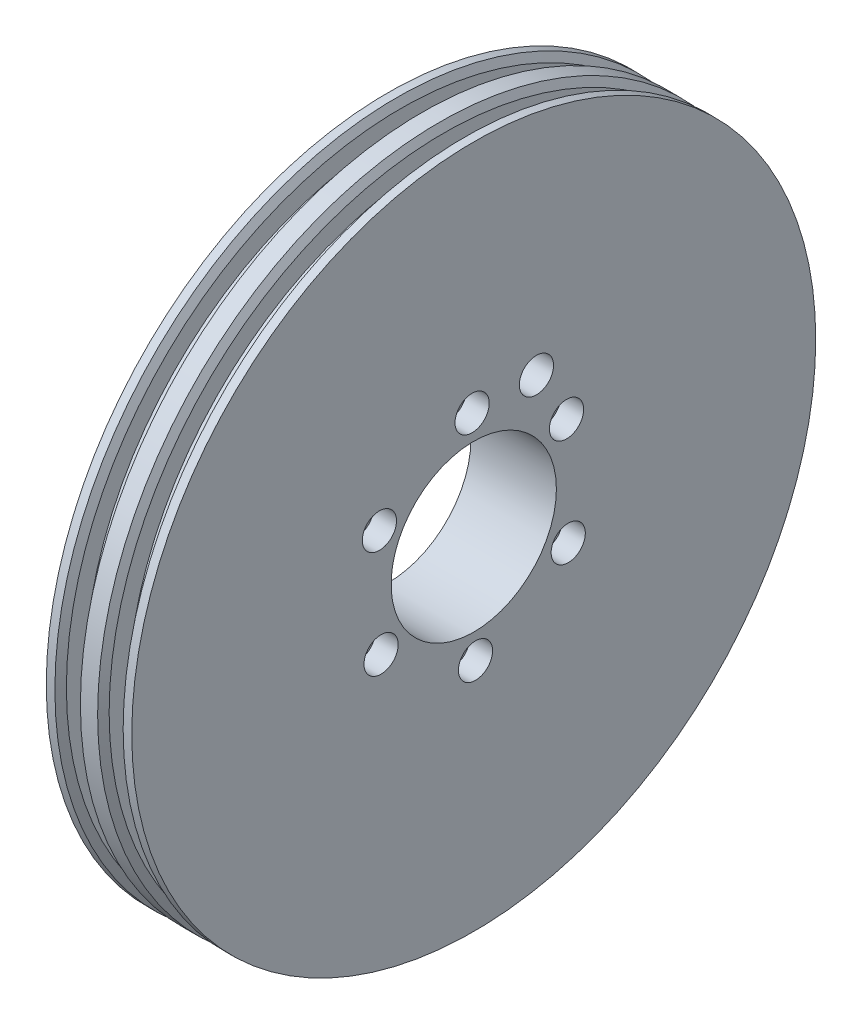
SolidWorks part; units mm, degrees
ref_plane "Front Plane" through (0, 0, 0) normal (0, 0, 1) x (1, 0, 0)
ref_plane "Top Plane" through (0, 0, 0) normal (0, 1, 0) x (1, 0, 0)
ref_plane "Right Plane" through (0, 0, 0) normal (1, 0, 0) x (0, 0, -1)
sketch "Sketch1" plane through (0, 0, 0) normal (1, 0, 0) x (0, 0, -1)
  circle A0 centre (0, 0) radius 14.5
  circle A1 centre (0, 0) radius 60
  dimension "D1" = 29
  dimension "D2" = 120
extrude "Boss-Extrude1" add sketch "Sketch1" along normal mid plane 15
sketch "Sketch3" plane through (7.5, 0, 0) normal (1, 0, 0) x (0, 0, -1)
  line L0 (0, 0) -> (0, 19) construction
  circle A0 centre (0, 19) radius 2
  circle A1 centre (16.4545, 9.5) radius 2
  circle A2 centre (16.4545, -9.5) radius 2
  circle A3 centre (0, -19) radius 2
  circle A4 centre (-16.4545, -9.5) radius 2
  circle A5 centre (-16.4545, 9.5) radius 2
  point P20 (0, 0)
  dimension "D1" = 19
  dimension "D2" = 6
extrude "Cut-Extrude2" cut sketch "Sketch3" against normal up to next
sketch "Sketch4" plane through (-7.5, 0, 0) normal (-1, 0, 0) x (0, 0, 1)
  circle A0 centre (0, 0) radius 23.5
  circle A1 centre (0, 0) radius 25
  circle A2 centre (0, 0) radius 22
  dimension "D1" = 1.5
  dimension "D2" = 1.5
extrude "Cut-Extrude3" cut sketch "Sketch4" against normal blind 3 contours A1 A0 | A0 A2 region at (-7.5, 0, -22.8353) region at (-7.5, 0, -24.2929)
sketch "Sketch5" plane through (0, 0, 0) normal (0, 0, 1) x (1, 0, 0)
  line L0 (3.75, 61.9907) -> (3.75, 57.996) construction
  line L2 (0, -60) -> (0, 60) construction
  line L3 (5.25, 55.496) -> (2.25, 55.496)
  line L4 (5.25, 55.496) -> (5.25, 58.7191)
  line L5 (5.25, 60.496) -> (2.25, 60.496)
  line L6 (2.25, 55.496) -> (2.25, 58.7191)
  line L7 (5.25, 55.496) -> (2.25, 60.496) construction
  line L8 (5.25, 60.496) -> (2.25, 55.496) construction
  line L13 (5.25, 58.7191) -> (6.2759, 60.496)
  line L14 (6.2759, 60.496) -> (5.25, 60.496)
  line L15 (1.2241, 60.496) -> (2.25, 60.496)
  line L16 (2.25, 58.7191) -> (1.2241, 60.496)
  line L17 (0, -66) -> (0, 66) construction
  line L18 (-5.25, 60.496) -> (-2.25, 55.496) construction
  line L19 (-5.25, 55.496) -> (-2.25, 60.496) construction
  line L20 (-2.25, 58.7191) -> (-1.2241, 60.496)
  line L21 (-1.2241, 60.496) -> (-2.25, 60.496)
  line L22 (-6.2759, 60.496) -> (-5.25, 60.496)
  line L23 (-5.25, 58.7191) -> (-6.2759, 60.496)
  line L24 (-2.25, 55.496) -> (-2.25, 58.7191)
  line L25 (-5.25, 60.496) -> (-2.25, 60.496)
  line L26 (-5.25, 55.496) -> (-5.25, 58.7191)
  line L27 (-5.25, 55.496) -> (-2.25, 55.496)
  dimension "D1" = 3.75
  dimension "D2" = 3
  dimension "D3" = 5
  dimension "D4" = 30
ref_axis "Axis1" through (7.5, 0, 0) along (-1, 0, 0)
revolve "Cut-Revolve2" cut sketch "Sketch5" angle 360 about axis through (7.5, 0, 0) along (-1, 0, 0)
sketch "Sketch6" plane through (7.5, 0, 0) normal (1, 0, 0) x (0, 0, -1)
  circle A0 centre (-16.5542, 9.2009) radius 3
  circle A1 centre (-0.2869, 18.9372) radius 3
  circle A2 centre (16.2786, 9.7174) radius 3
  circle A3 centre (16.5768, -9.2387) radius 3
  circle A4 centre (0.3094, -18.9749) radius 3
  circle A5 centre (-16.256, -9.7551) radius 3
  point P16 (0.0113, -0.0189)
  dimension "D1" = 6
extrude "Cut-Extrude4" cut sketch "Sketch6" against normal blind 4
sketch "Sketch7" plane through (-7.5, 0, 0) normal (-1, 0, 0) x (0, 0, 1)
  line L0 (0, 0) -> (-11, 19.0526) construction
  line L1 (0, 0) -> (0, 2.9604) construction
  circle A1 centre (-11, 19.0526) radius 3
  point P11 (0, 0)
  dimension "D1" = 30
  dimension "D3" = 22
extrude "Cut-Extrude5" cut sketch "Sketch7" against normal up to next
